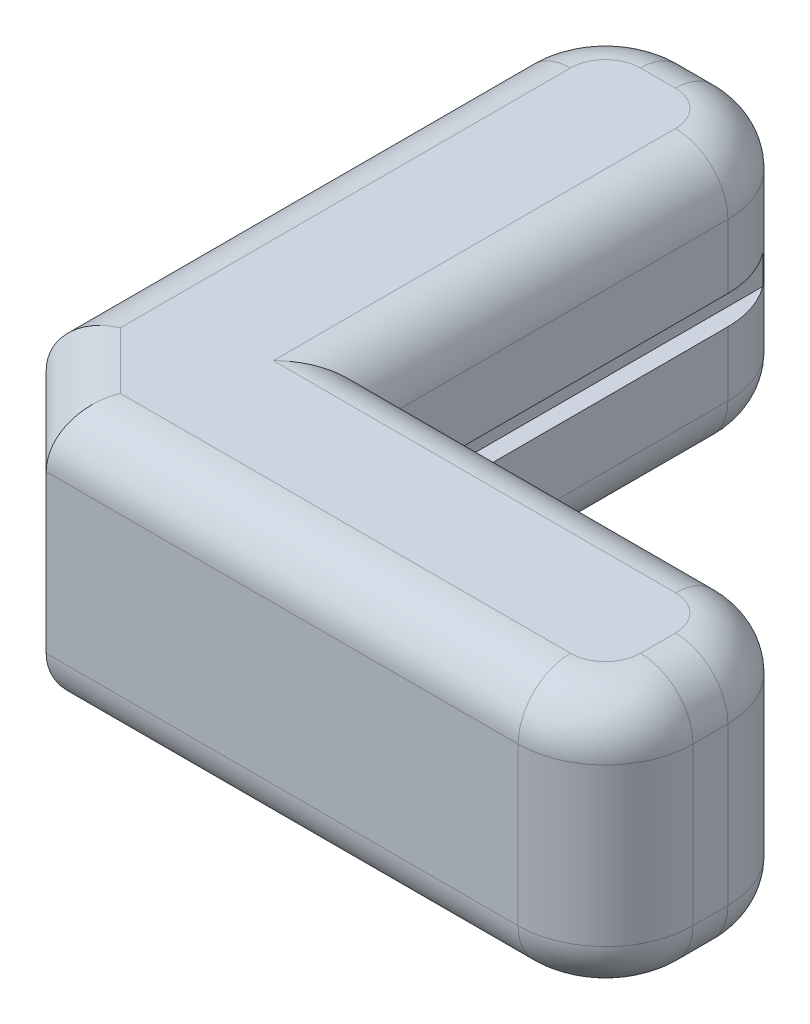
SolidWorks part; units mm, degrees
ref_plane "Front Plane" through (0, 0, 0) normal (0, 0, 1) x (1, 0, 0)
ref_plane "Top Plane" through (0, 0, 0) normal (0, 1, 0) x (1, 0, 0)
ref_plane "Right Plane" through (0, 0, 0) normal (1, 0, 0) x (0, 0, -1)
sketch "Sketch1" plane through (0, 0, 0) normal (0, 1, 0) x (1, 0, 0)
  line L0 (0, 25) -> (0, 0)
  line L1 (0, 0) -> (25, 0)
  line L2 (0, 25) -> (-12, 25)
  line L3 (25, 0) -> (25, -12)
  line L4 (-12, 25) -> (-12, -7)
  line L5 (-7, -12) -> (25, -12)
  line L6 (-12, -7) -> (-7, -12)
  point P7 (-12, -12)
  dimension "D1" = 25
  dimension "D2" = 12
extrude "Boss-Extrude1" add sketch "Sketch1" along normal mid plane 15
sketch "Sketch3" plane through (0, 0, 0) normal (0, 0, -1) x (-1, 0, 0)
  line L0 (0, 0) -> (-25, 0) construction
  line L1 (-25, 7.5) -> (-25, -7.5) construction
  line L3 (-25, 0.825) -> (0, 0.825)
  line L4 (-25, 0.825) -> (-25, -0.825)
  line L5 (-25, -0.825) -> (0, -0.825)
  line L6 (0, 0.825) -> (0, -0.825)
  line L7 (0, 7.5) -> (0, -7.5) construction
  point P9 (0, 0)
  point P10 (0, 0)
  point P11 (0, 0)
  point P12 (-25, 0)
  dimension "D1" = 1.65
extrude "Cut-Extrude1" cut sketch "Sketch3" against normal blind 1
sketch "Sketch4" plane through (0, 0, -25) normal (0, 0, -1) x (-1, 0, 0)
  line L0 (-25, -0.825) -> (0, -0.825) construction
  line L1 (0, 0.825) -> (1, 0.825)
  line L2 (0, 0.825) -> (0, -0.825)
  line L3 (0, -0.825) -> (1, -0.825)
  line L4 (1, 0.825) -> (1, -0.825)
  dimension "D1" = 1
extrude "Cut-Extrude2" cut sketch "Sketch4" against normal up to surface (26 mm away) up to face at (12.5, 0, 1)
fillet "Fillet1" radius 5 4 edges at (25, -4.1625, 0) (25, 0, 12) (0, 4.1625, -25) (-12, 0, -25)
fillet "Fillet2" radius 3 22 edges at (0, -7.5, -10) (-1.4645, -7.5, -23.5355) (-6, -7.5, -25) (-10.5355, -7.5, -23.5355) (-12, -7.5, -6.5) (-9.5, -7.5, 9.5) (6.5, -7.5, 12) (23.5355, -7.5, 10.5355) (25, -7.5, 6) (23.5355, -7.5, 1.4645) (10, -7.5, 0) (23.5355, 7.5, 10.5355) (6.5, 7.5, 12) (-9.5, 7.5, 9.5) (-12, 7.5, -6.5) (-10.5355, 7.5, -23.5355) (-6, 7.5, -25) (-1.4645, 7.5, -23.5355) (0, 7.5, -10) (10, 7.5, 0) (23.5355, 7.5, 1.4645) (25, 7.5, 6)
sketch "Sketch5" plane through (-9.5, 0, 9.5) normal (-0.7071, 0, 0.7071) x (0.7071, 0, 0.7071)
  circle A0 centre (0, 0) radius 2
  dimension "D1" = 4
extrude "Cut-Extrude3" cut sketch "Sketch5" against normal blind 7
sketch "Sketch6" plane through (-9.5, 0, 9.5) normal (-0.7071, 0, 0.7071) x (0.7071, 0, 0.7071)
  circle A0 centre (0, 0) radius 2 construction
  circle A1 centre (0, 0) radius 2
curve "Helix/Spiral1" pitch 5 height 6.25 radius 2 centre (-9.5, 0, 9.5) axis (0.7071, 0, -0.7071) start towards (0.7071, 0, 0.7071)
sketch "Sketch8" plane through (0, 0, 0) normal (0, 1, 0) x (1, 0, 0)
  line L2 (-7.5555, -10.3839) -> (-7.0251, -11.9749)
  line L3 (-7.0251, -11.9749) -> (-8.6161, -11.4445)
  line L4 (-7.5555, -10.3839) -> (-8.0858, -10.9142)
  line L5 (-12, -7) -> (-7, -12) construction
  line L6 (-8.0858, -10.9142) -> (-8.6161, -11.4445)
  spline S1 degree 3 poles (-8.0858, -10.9142) (-8.0125, -10.841) (-7.9383, -10.6194) (-8.0321, -10.0841) (-8.2818, -9.3924) (-8.6161, -8.6161) (-8.9504, -7.8399) (-9.2002, -7.1481) (-9.2938, -6.6126) (-9.1833, -6.2812) (-8.8518, -6.1707) (-8.3163, -6.2643) (-7.394, -6.5973) (-6.3027, -7.0994) (-5.3804, -7.4324) (-4.8449, -7.526) (-4.5134, -7.4155) (-4.4029, -7.0841) (-4.4966, -6.5484) (-4.746, -5.8575) (-4.9697, -5.3379) (-5.0806, -5.0806) knots 0 0 0 0 0.05 0.1 0.15 0.2 0.25 0.3 0.35 0.4 0.45 0.5 0.55 0.65 0.7 0.75 0.8 0.85 0.9 0.95 1 1 1 1 construction
  point P0 (-7.0251, -11.9749)
  dimension "D1" = 0.75
  dimension "D2" = 1.5
sweep "Cut-Sweep1" cut profiles "Sketch8" path "Helix/Spiral1" align with end faces yes
